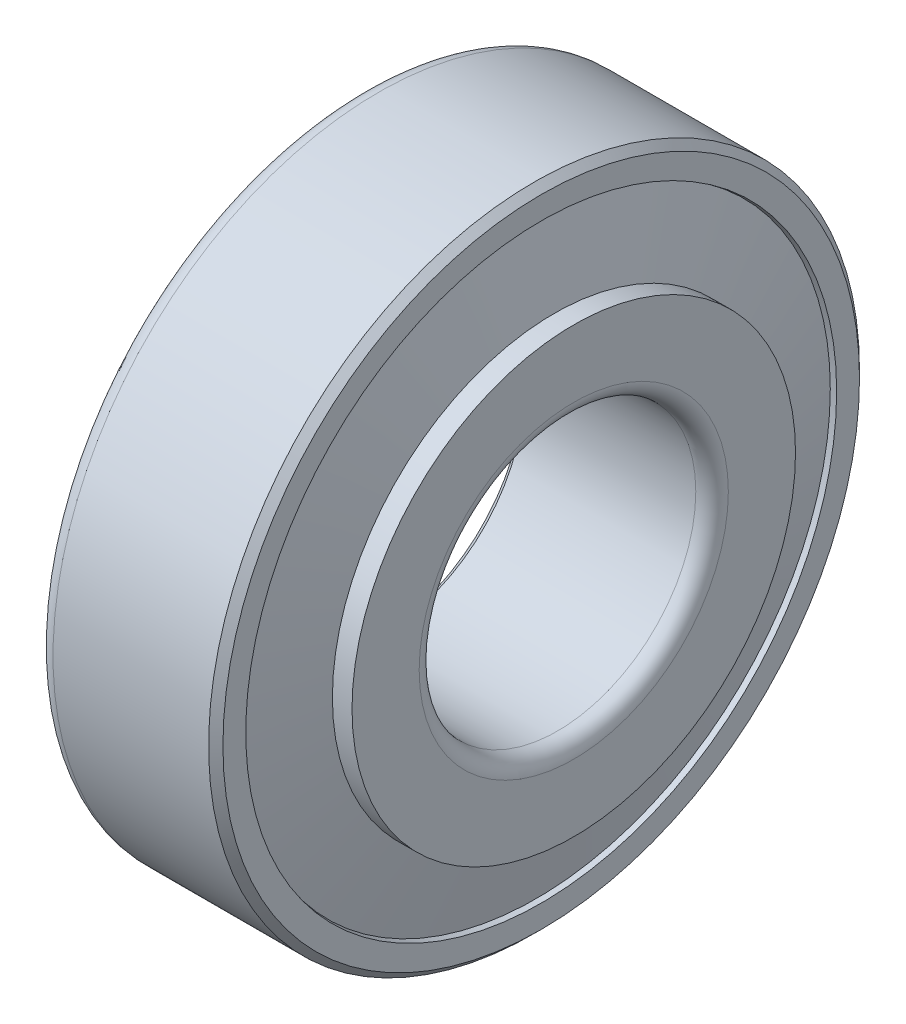
SolidWorks part; units mm, degrees
revolve "OuterRace" add sketch "OutRacSke" angle 360 about L5 other way angle 28.04 reverse direction yes
sketch "OutRacSke" plane through (0, 0, 0) normal (0, 0, 1) x (1, 0, 0)
  line L0 (-2, 18.1567) -> (-13, 15.704)
  line L1 (-13, 15.704) -> (-13, 19)
  line L2 (-12, 20) -> (-2.44, 20)
  line L3 (-2.44, 20) -> (-2, 19.56)
  line L4 (-2, 19.56) -> (-2, 18.1567)
  line L5 (-42.5, 0) -> (42.5, 0) construction
  arc A0 (-13, 19) -> (-12, 20) centre (-12, 19) cw
  dimension "D8" = 45
  dimension "Tangle" = 12.57
ref_plane "Plane1" through (0, 0, 0) normal (0, 0, 1) x (1, 0, 0)
ref_plane "Plane2" through (0, 0, 0) normal (0, 1, 0) x (1, 0, 0)
ref_plane "Plane3" through (0, 0, 0) normal (1, 0, 0) x (0, 0, -1)
sketch "Clipboard" plane through (0, 0, 0) normal (0, 0, 1) x (1, 0, 0)
  line L0 (0, 0) -> (10, 0) construction
  line L1 (0, 0) -> (31.3889, -1.0961)
  line L2 (0, 0) -> (16.9896, 0.5933)
  line L3 (0, 0) -> (39.9756, -1.396)
  line L4 (0, 0) -> (-9.8985, -0.1728)
  line L5 (0, 0) -> (-5.175, 13)
  dimension "Roller_diameter" = 5.175
  dimension "cyl_len" = 9.9
sketch "RolDetSke" plane through (0, 0, 0) normal (0, 0, 1) x (1, 0, 0)
  line L0 (-11.4369, 13.4811) -> (-12, 16.0066)
  line L1 (-11.4369, 13.4811) -> (-1.7742, 15.6357)
  line L2 (-2.3373, 18.1612) -> (-1.7742, 15.6357)
  line L4 (-40.6277, 6.9722) -> (8.5738, 17.9431) construction
  line L5 (-2.3373, 18.1612) -> (-12, 16.0066)
  line L9 (-2, 18.1567) -> (-13, 15.704) construction
  dimension "Roller_diameter" = 5.175
  dimension "dy" = 16.0066
  dimension "D2" = 12
  dimension "cyl_len" = 9.9
revolve "RollerDetailed" [suppressed] add sketch "RolDetSke" angle 360 about L4 reverse direction yes
sketch "RolSimSke" plane through (0, 0, 0) normal (0, 0, 1) x (1, 0, 0)
  line L0 (0, 0) -> (-32, 0) construction
  line L1 (-12, 16.0066) -> (-2.3373, 18.1612)
  line L2 (-12, 16.0066) -> (-10.8738, 10.9557)
  line L3 (-10.8738, 10.9557) -> (-1.211, 13.1102)
  line L4 (-2.3373, 18.1612) -> (-1.211, 13.1102)
  dimension "Roller_diameter" = 5.175
  dimension "dy" = 16.0066
  dimension "dx" = 12
  dimension "Tangle" = 12.57
revolve "RollersSimplified" add sketch "RolSimSke" angle 360 about L0
ref_axis "Axis1" through (-50, 0, 0) along (1, 0, 0)
pattern_circular "RollersDetailed" [suppressed] count 2 every 180 about axis through (-50, 0, 0) along (1, 0, 0)
sketch "InsRacSke" plane through (0, 0, 0) normal (0, 0, 1) x (1, 0, 0)
  line L0 (-10.9258, 11.2144) -> (-12, 11.2144)
  line L1 (-13, 19) -> (-13, -19) construction
  line L2 (-12, 11.2144) -> (-12, 8.94)
  line L3 (-12, 8.94) -> (-11.56, 8.5)
  line L4 (-11.56, 8.5) -> (-1, 8.5)
  line L5 (0, 9.5) -> (0, 13.6277)
  line L6 (0, 13.6277) -> (-1.2054, 13.6277)
  line L7 (-1.2054, 13.6277) -> (-1.2054, 13.1102)
  line L8 (-1.2054, 13.1102) -> (-10.8681, 10.9557)
  line L9 (-10.8681, 10.9557) -> (-10.9258, 11.2144)
  line L10 (-42.5, 0) -> (42.5, 0) construction
  arc A0 (-1, 8.5) -> (0, 9.5) centre (-1, 9.5) ccw
  dimension "Tangle" = 12.57
  dimension "cyl_len" = 9.9
  dimension "dy" = 10.9557
  dimension "dx" = 10.8681
  dimension "D11" = 45
  dimension "D2" = 13
revolve "InnerRace" add sketch "InsRacSke" angle 360 about L10 reverse direction yes
sketch "CagSpiSke" plane through (0, 0, 0) normal (0, 0, 1) x (1, 0, 0)
  line L3 (-1.291, 15.6638) -> (-11.4369, 13.4015)
  line L4 (-11.6985, 12.9897) -> (-11.5484, 12.3162)
  line L6 (-42.5, 0) -> (42.5, 0) construction
  arc A1 (-11.4369, 13.4015) -> (-11.6985, 12.9897) centre (-11.3618, 13.0648) ccw
  dimension "Tangle" = 12.57
  dimension "radius" = 0.345
  dimension "dx" = 11.4369
  dimension "dy" = 13.4015
  dimension "offset" = 1.035
revolve "CageSpine" [suppressed] add sketch "CagSpiSke" angle 0.001 about L6 wall 0.8625
equation "\"OD@OutRacSke\" = \"Race_OD@Clipboard\""
equation "\"cup_SID@OutRacSke\" = \"Race_ID@Clipboard\""
equation "\"chamfer@OutRacSke\" = \"cup_width@OutRacSke\" / 25"
equation "\"offset@OutRacSke\" = \"OA_width@Clipboard\""
equation "\"D2@RolDetSke\" = \"offset@OutRacSke\" - \"cup_radius@OutRacSke\""
equation "\"dy@RolDetSke\" =  ( ( \"Race_ID@Clipboard\" / 2 ) + ( \"cup_radius@OutRacSke\" ) * tan(\"Tangle@OutRacSke\" * 3.141592654/180) ) * 1.005"
equation "\"cyl_len@RolDetSke\" = \"cyl_len@Clipboard\""
equation "\"Roller_diameter@RolDetSke\" = \"Roller_diameter@Clipboard\""
equation "\"dx@RolSimSke\" = \"offset@OutRacSke\" - \"cup_radius@OutRacSke\""
equation "\"dy@RolSimSke\" =  ( ( \"Race_ID@Clipboard\" / 2 ) + ( \"cup_radius@OutRacSke\" ) * tan(\"Tangle@OutRacSke\" * 3.141592654/180) ) * 1.005"
equation "\"Cyl_Len@RolSimSke\" = \"cyl_len@Clipboard\""
equation "\"Roller_diameter@RolSimSke\" = \"Roller_diameter@Clipboard\""
equation "\"Bore@InsRacSke\" = \"Bore@Clipboard\""
equation "\"Tangle@InsRacSke\" = \"Tangle@OutRacSke\""
equation "\"cyl_len@InsRacSke\" = \"cyl_len@Clipboard\""
equation "\"chamfer@InsRacSke\" = \"chamfer@OutRacSke\""
equation "\"D2@InsRacSke\" = \"OA_width@Clipboard\""
equation "\"dx@InsRacSke\" = \"offset@OutRacSke\" - \"cup_radius@OutRacSke\" -  (  \"Roller_diameter@Clipboard\" * 1.005 )  * sin(\"Tangle@InsRacSke\" * 3.141592654/180)"
equation "\"dy@InsRacSke\" = ( ( \"Race_ID@Clipboard\" / 2 ) + ( \"cup_radius@OutRacSke\" ) * tan(\"Tangle@OutRacSke\" * 3.141592654/180) ) * 1.005 -  ( \"Roller_diameter@Clipboard\" )  * cos(\"Tangle@InsRacSke\" * 3.141592654/180) "
equation "\"front_groove@InsRacSke\" = \"Groove_dp@InsRacSke\" / 2"
equation "\"Tangle@CagSpiSke\" = \"Tangle@OutRacSke\""
equation "\"dx@CagSpiSke\" = ( \"offset@OutRacSke\" - \"cup_radius@OutRacSke\" ) -  (  \"Roller_diameter@Clipboard\" / 2  )  * sin(\"Tangle@InsRacSke\" * 3.141592654/180)"
equation "\"dy@CagSpiSke\" = ( ( \"Race_ID@Clipboard\" / 2 ) + ( \"cup_radius@OutRacSke\" ) * tan(\"Tangle@OutRacSke\" * 3.141592654/180) )  -  ( \"Roller_diameter@Clipboard\" / 2 )  * cos(\"Tangle@InsRacSke\" * 3.141592654/180) "
equation "\"length@CagSpiSke\" = \"cyl_len@Clipboard\" * 1.05"
equation "\"offset@CagSpiSke\" = \"Roller_diameter@Clipboard\" / 5"
equation "\"radius@CagSpiSke\" = \"offset@CagSpiSke\" / 3"
equation "\"D3@CageSpine\" = \"Roller_diameter@Clipboard\" / 6"
equation "\"Max_count@Clipboard\" = int( 3.14159265 / atn(( \"Roller_diameter@Clipboard\" / 2) / sqr( \"dy@CagSpiSke\"  *  \"dy@CagSpiSke\" - ( \"Roller_diameter@Clipboard\" / 2) *  ( \"Roller_diameter@Clipboard\" / 2))))"
equation "\"Max_count@Clipboard\" = ((sgn( \"Max_count@Clipboard\" - \"Count@Clipboard\" )-1)*( \"Max_count@Clipboard\" - \"Count@Clipboard\" ))/-2+ \"Count@Clipboard\""
equation "\"Count@RollersDetailed\" = int( \"Show_count@Clipboard\" ) "
equation "\"Count@RollersDetailed\" = ((sgn( \"Count@RollersDetailed\" - \"Max_count@Clipboard\" )-1)*( \"Count@RollersDetailed\" - \"Max_count@Clipboard\" ))/-2+ \"Max_count@Clipboard\""
equation "\"Count@RollersDetailed\" = ((sgn( \"Count@RollersDetailed\" - \"Min_count@Clipboard\" )+1)*( \"Count@RollersDetailed\" - \"Min_count@Clipboard\"))/2 +\"Min_count@Clipboard\""
equation "\"Angle@RollersDetailed\" = 360.0 / \"Max_count@Clipboard\""
equation "\"Angle@CageSpine\" =  \"Angle@RollersDetailed\" * ( \"Count@RollersDetailed\" -1 + int( \"Count@RollersDetailed\" / \"Max_count@Clipboard\" ) )  + 0.001 -  int( \"Count@RollersDetailed\" / \"Max_count@Clipboard\" ) * 0.001"
equation "\"Angle@CageSpine\" =  \"Angle@CageSpine\" * int( \"Min_count@Clipboard\" / 2) + int(1 / \"Min_count@Clipboard\")  * 0.001"
equation "\"Tangle@RolSimSke\" = \"Tangle@OutRacSke\""
